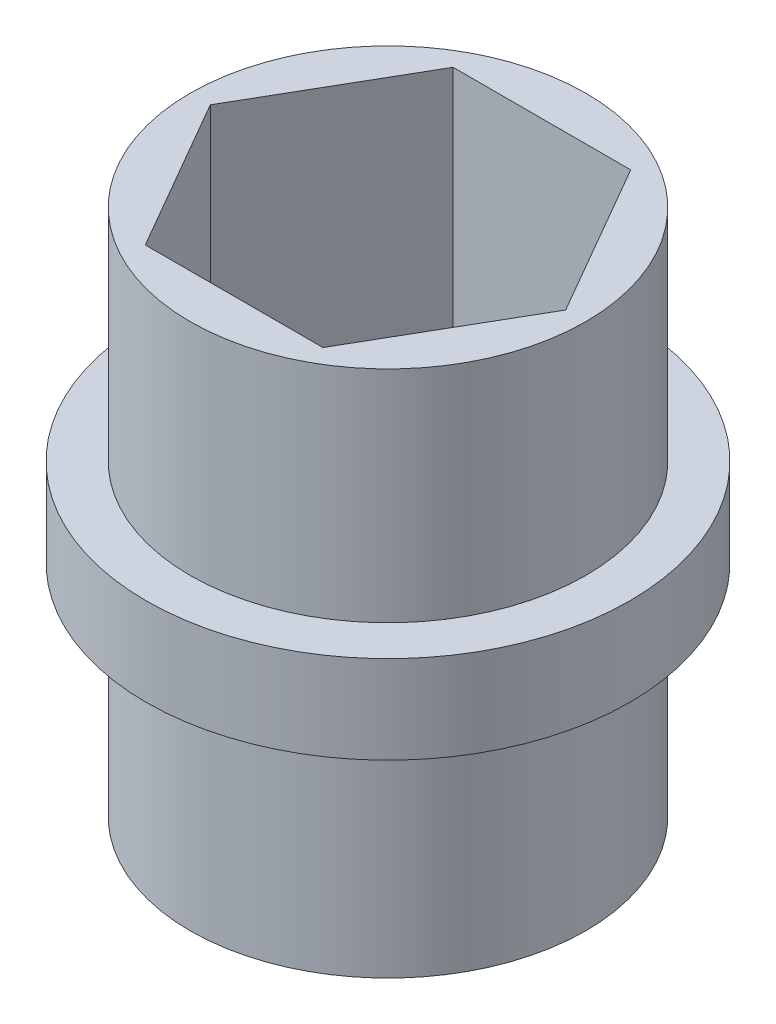
SolidWorks part; units mm, degrees
ref_plane "Front Plane" through (0, 0, 0) normal (0, 0, 1) x (1, 0, 0)
ref_plane "Top Plane" through (0, 0, 0) normal (0, 1, 0) x (1, 0, 0)
ref_plane "Right Plane" through (0, 0, 0) normal (1, 0, 0) x (0, 0, -1)
sketch "Sketch2" plane through (0, 0, 0) normal (0, 1, 0) x (1, 0, 0)
  line L1 (4.0415, 0) -> (2.0207, 3.5)
  line L2 (2.0207, 3.5) -> (-2.0207, 3.5)
  line L3 (-2.0207, 3.5) -> (-4.0415, 0)
  line L4 (-4.0415, 0) -> (-2.0207, -3.5)
  line L5 (-2.0207, -3.5) -> (2.0207, -3.5)
  line L6 (2.0207, -3.5) -> (4.0415, 0)
  circle A0 centre (0, 0) radius 4.5
  circle A1 centre (0, 0) radius 3.5 construction
  dimension "D1" = 9
  dimension "D2" = 7
extrude "Boss-Extrude1" add sketch "Sketch2" along normal blind 12
ref_plane "Plane1" through (0, 6, 0) normal (0, -1, 0) x (-1, 0, 0)
sketch "Sketch3" plane through (0, 6, 0) normal (0, -1, 0) x (-1, 0, 0)
  circle A0 centre (0, 0) radius 4.5 construction
  circle A1 centre (0, 0) radius 4.5
  circle A2 centre (0, 0) radius 5.5
  dimension "D1" = 1
extrude "Boss-Extrude2" add sketch "Sketch3" along normal mid plane 2
